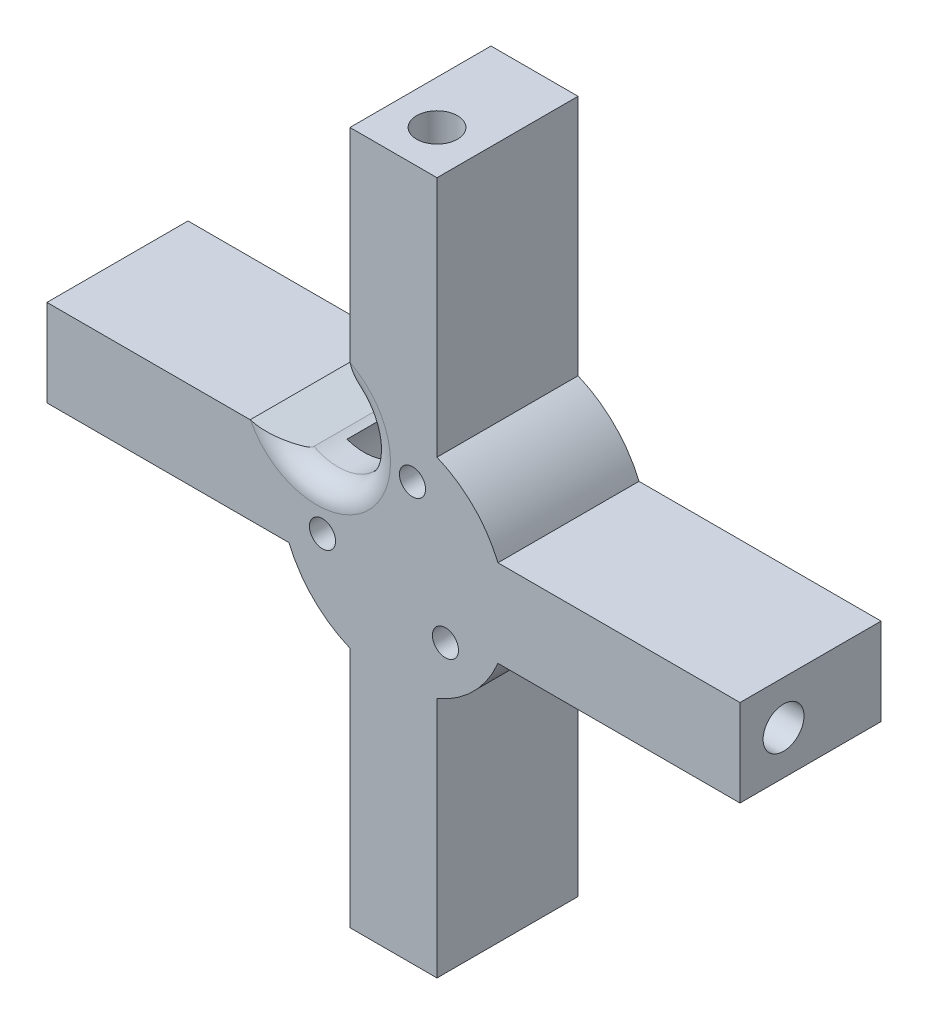
SolidWorks part; units mm, degrees
ref_plane "Front Plane" through (0, 0, 0) normal (0, 0, 1) x (1, 0, 0)
ref_plane "Top Plane" through (0, 0, 0) normal (0, 1, 0) x (1, 0, 0)
ref_plane "Right Plane" through (0, 0, 0) normal (1, 0, 0) x (0, 0, -1)
sketch "Sketch4" plane through (0, 0, 0) normal (0, 0, 1) x (1, 0, 0)
  line L12 (-5, 39.8) -> (5, 39.8)
  line L14 (0, 0) -> (0, 39.8)
  line L15 (-5, 39.8) -> (-5, 12)
  line L16 (5, 39.8) -> (5, 12)
  line L17 (39.8, 5) -> (12, 5)
  line L18 (39.8, 5) -> (39.8, -5)
  line L19 (39.8, -5) -> (12, -5)
  line L20 (5, -39.8) -> (5, -12)
  line L21 (5, -39.8) -> (-5, -39.8)
  line L22 (-5, -39.8) -> (-5, -12)
  line L23 (-39.8, -5) -> (-12, -5)
  line L24 (-39.8, -5) -> (-39.8, 5)
  line L25 (-39.8, 5) -> (-12, 5)
  circle A4 centre (0, 0) radius 13
  point P5 (0, 39.8)
  point P24 (0, 0)
  dimension "D2" = 39.8
  dimension "D3" = 26
  dimension "D1" = 10
  dimension "D4" = 4
extrude "Boss-Extrude1" add sketch "Sketch4" against normal blind 22.7 contours A4 L22 L21 L20 | A4 L19 L18 L17 | A4 L25 L24 L23 | A4 | A4 L14 L12 L15 | A4 L16 L12 L14 region at (-2.5152, 26.2344, 0) region at (2.5152, 26.2344, 0) region at (-2.4774, 12.387, 0) region at (-26.2344, 0, 0) region at (26.2344, 0, 0) region at (0, -26.2344, 0)
sketch "Sketch5" plane through (0, 0, 0) normal (0, 0, 1) x (1, 0, 0)
  line L0 (-5, 16.4565) -> (-3.5231, 11.6214)
  line L1 (-5, 39.8) -> (-5, 12) construction
  line L2 (-8.1541, -2.1849) -> (5.9692, -5.9692) construction
  line L3 (5.9692, -5.9692) -> (2.1849, 8.1541) construction
  line L4 (2.1849, 8.1541) -> (-8.1541, -2.1849) construction
  line L5 (0, 0) -> (2.1849, 8.1541) construction
  line L6 (0, 0) -> (5.9692, -5.9692) construction
  line L7 (0, 0) -> (-8.1541, -2.1849) construction
  line L8 (-8.8388, 8.8388) -> (-8.1541, -2.1849) construction
  line L9 (2.1849, 8.1541) -> (-8.8388, 8.8388) construction
  line L12 (-5, 16.4565) -> (-6.9295, 14.5269)
  line L13 (-39.8, 5) -> (-12, 5) construction
  line L14 (-16.4565, 5) -> (-11.6214, 3.5231)
  line L15 (-14.5269, 6.9295) -> (-16.4565, 5)
  circle A3 centre (0, 0) radius 12.5
  circle A5 centre (2.1849, 8.1541) radius 1.5
  circle A6 centre (-8.1541, -2.1849) radius 1.5
  circle A7 centre (5.9692, -5.9692) radius 1.5
  arc A8 (-6.9295, 14.5269) -> (-14.5269, 6.9295) centre (-8.8388, 8.8388) ccw
  arc A9 (-11.6214, 3.5231) -> (-3.5231, 11.6214) centre (-8.8388, 8.8388) ccw
  point P24 (0, 0)
  dimension "D2" = 3
  dimension "D3" = 8.4418
  dimension "D12" = 12
  dimension "D4" = 2.7288
  dimension "D5" = 5.0556
extrude "Cut-Extrude1" cut sketch "Sketch5" against normal blind 70 contours A8 L15 L14 A9 L0 L12 | A5 | A6 | A7
sketch "Sketch6" plane through (0, 0, -22.7) normal (0, 0, -1) x (-1, 0, 0)
  circle A1 centre (0, 0) radius 11.25
  dimension "D1" = 22.5
extrude "Cut-Extrude3" cut sketch "Sketch6" against normal blind 17.25 and the other way blind 17.25 contours A1
sketch "Sketch7" plane through (0, 0, -5.45) normal (0, 0, -1) x (-1, 0, 0)
  circle A0 centre (-2.1849, 8.1541) radius 2
  circle A3 centre (-5.9692, -5.9692) radius 2
  circle A4 centre (8.1541, -2.1849) radius 2
  dimension "D1" = 4
  dimension "D2" = 4
  dimension "D3" = 4
extrude "Cut-Extrude4" cut sketch "Sketch7" against normal blind 3
sketch "Sketch8" plane through (-5, 0, 0) normal (-1, 0, 0) x (0, 0, 1)
  line L0 (-22.7, 39.8) -> (-16.2, 39.8)
  line L1 (-22.7, 39.8) -> (0, 39.8) construction
  line L2 (-16.2, 39.8) -> (-16.2, -39.8)
  line L3 (-22.7, -39.8) -> (0, -39.8) construction
  line L4 (-16.2, -39.8) -> (-22.7, -39.8)
  line L5 (-22.7, -39.8) -> (-22.7, 39.8)
  dimension "D1" = 6.5
extrude "Cut-Extrude5" cut sketch "Sketch8" against normal blind 66 and the other way blind 58
sketch "Sketch9" plane through (0, 39.8, 0) normal (0, 1, 0) x (1, 0, 0)
  circle A0 centre (0, 5) radius 2.35
  circle A1 centre (0, 5) radius 1.55
  dimension "D2" = 4.7
  dimension "D3" = 3.1
  dimension "D1" = 5
extrude "Cut-Extrude7" cut sketch "Sketch9" against normal blind 4 contours A1 | A0
extrude "Cut-Extrude20" cut sketch "Sketch9<3>" against normal blind 12 contours A1 region at (0, 39.8, -5)
sketch "Sketch9<3>" plane through (0, 39.8, 0) normal (0, 1, 0) x (1, 0, 0) same geometry as "Sketch9"
sketch "Sketch19" plane through (39.8, 0, 0) normal (1, 0, 0) x (0, 0, -1)
  circle A0 centre (5, 0) radius 2.35
  circle A1 centre (5, 0) radius 1.55
  dimension "D1" = 4.7
  dimension "D2" = 3.1
  dimension "D3" = 5
sketch "Sketch20" plane through (0, -39.8, 0) normal (0, -1, 0) x (1, 0, 0)
  circle A0 centre (0, -5) radius 2.35
  circle A1 centre (0, -5) radius 1.55
  dimension "D2" = 3.1
  dimension "D3" = 4.7
  dimension "D1" = 5
sketch "Sketch21" plane through (-39.8, 0, 0) normal (-1, 0, 0) x (0, 0, 1)
  line L0 (-16.2, 0) -> (-5, 0) construction
  line L1 (-16.2, -5) -> (-16.2, 5) construction
  circle A0 centre (-5, 0) radius 1.55
  circle A1 centre (-5, 0) radius 2.35
  dimension "D1" = 3.1
  dimension "D2" = 4.7
extrude "Cut-Extrude22" cut sketch "Sketch21" against normal blind 4
extrude "Cut-Extrude23" cut sketch "Sketch21<2>" against normal blind 12 contours A0 region at (-39.8, 0, -5)
sketch "Sketch21<2>" plane through (-39.8, 0, 0) normal (-1, 0, 0) x (0, 0, 1) same geometry as "Sketch21"
extrude "Cut-Extrude24" cut sketch "Sketch19" against normal blind 4
extrude "Cut-Extrude25" cut sketch "Sketch19<2>" against normal blind 12 contours A1 region at (39.8, 0, -5)
sketch "Sketch19<2>" plane through (39.8, 0, 0) normal (1, 0, 0) x (0, 0, -1) same geometry as "Sketch19"
extrude "Cut-Extrude26" cut sketch "Sketch20" against normal blind 4
extrude "Cut-Extrude27" cut sketch "Sketch20<2>" against normal blind 12 contours A1 region at (0, -39.8, -5)
sketch "Sketch20<2>" plane through (0, -39.8, 0) normal (0, -1, 0) x (1, 0, 0) same geometry as "Sketch20"
fillet "Fillet2" radius 2.5 1 edges at (-4.5962, 4.5962, 0)
sketch "Sketch22" plane through (0, 0, -5.45) normal (0, 0, -1) x (-1, 0, 0)
  line L0 (-11.25, 0) -> (11.25, 0) construction
  arc A0 (3.1667, 10.7951) -> (10.7951, 3.1667) centre (0, 0) ccw construction
  arc A1 (3.1667, 10.7951) -> (10.7951, 3.1667) centre (0, 0) ccw construction
  text T0 "V"
extrude "Boss-Extrude2" add sketch "Sketch22" along normal blind 0.5
